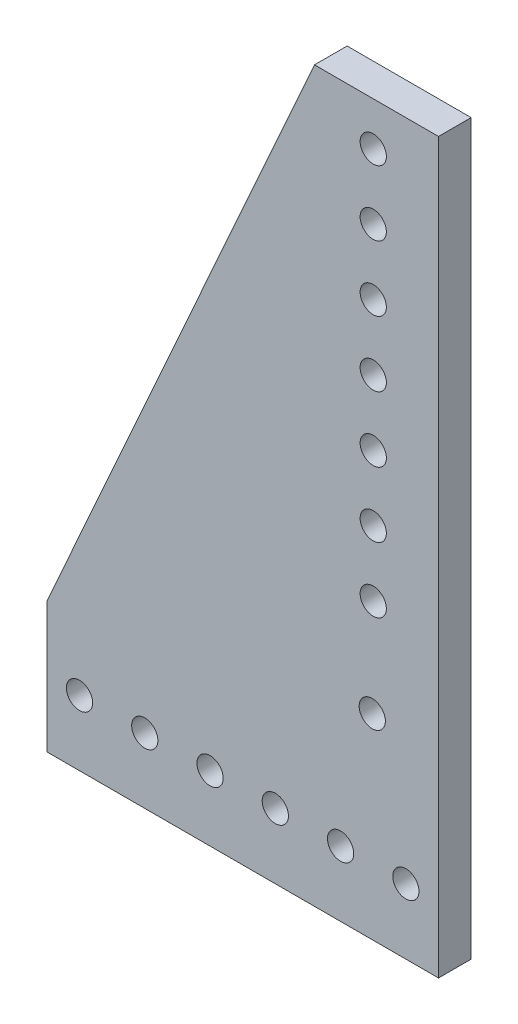
SolidWorks part; units mm, degrees
material "6061-T6 (SS)"
ref_plane "Front Plane" through (0, 0, 0) normal (0, 0, 1) x (1, 0, 0)
ref_plane "Top Plane" through (0, 0, 0) normal (0, 1, 0) x (1, 0, 0)
ref_plane "Right Plane" through (0, 0, 0) normal (1, 0, 0) x (0, 0, -1)
sketch "Sketch1" plane through (0, 0, 0) normal (0, 0, 1) x (1, 0, 0)
  line L1 (-128, 138.6667) -> (49.8, 138.6667)
  line L2 (-128, 138.6667) -> (-128, -115.3333)
  line L3 (-128, -115.3333) -> (49.8, -115.3333)
  line L4 (49.8, 138.6667) -> (49.8, -115.3333)
  dimension "D1" = 254
  dimension "D2" = 177.8
extrude "Boss-Extrude1" add sketch "Sketch1" along normal blind 6.35
sketch "Sketch2" plane through (0, 0, 6.35) normal (0, 0, 1) x (1, 0, 0)
  line L0 (-39.1, -115.3333) -> (-39.1, 138.6667) construction
  line L1 (-128, -115.3333) -> (49.8, -115.3333) construction
  line L2 (49.8, 138.6667) -> (-128, 138.6667) construction
  line L3 (-39.1, -108.9833) -> (-39.1, -96.2833) construction
  circle A0 centre (-39.1, -108.9833) radius 2.5527 construction
  circle A1 centre (-39.1, -96.2833) radius 2.5527 construction
  circle A2 centre (-39.1, -83.5833) radius 2.5527 construction
  circle A3 centre (-39.1, -70.8833) radius 2.5527 construction
  circle A4 centre (-39.1, -58.1833) radius 2.5527
  circle A5 centre (-39.1, -45.4833) radius 2.5527
  circle A6 centre (-39.1, -32.7833) radius 2.5527
  circle A7 centre (-39.1, -20.0833) radius 2.5527
  circle A8 centre (-39.1, -7.3833) radius 2.5527
  circle A9 centre (-39.1, 5.3167) radius 2.5527
  circle A10 centre (-39.1, 18.0167) radius 2.5527
  circle A11 centre (-39.1, 30.7167) radius 2.5527
  circle A12 centre (-39.2905, -77.2333) radius 2.5527
  dimension "D1" = 6.35
  dimension "D2" = 5.1054
  dimension "D5" = 5.1054
  dimension "D6" = 19.05
  dimension "D3" = 12.7
  dimension "D4" = 12
extrude "Cut-Extrude1" cut sketch "Sketch2" against normal through all
sketch "Sketch3" plane through (0, 0, 6.35) normal (0, 0, 1) x (1, 0, 0)
  line L0 (30.75, -102.6333) -> (-17.6342, -102.6333) construction
  line L1 (-128, -115.3333) -> (49.8, -115.3333) construction
  line L2 (49.8, -115.3333) -> (49.8, 138.6667) construction
  line L3 (30.75, -102.6333) -> (18.05, -102.6333) construction
  circle A0 centre (30.75, -102.6333) radius 2.5527
  circle A1 centre (18.05, -102.6333) radius 2.5527
  circle A2 centre (5.35, -102.6333) radius 2.5527
  circle A3 centre (-7.35, -102.6333) radius 2.5527
  circle A4 centre (-20.05, -102.6333) radius 2.5527
  circle A5 centre (-32.75, -102.6333) radius 2.5527
  circle A6 centre (-45.45, -102.6333) radius 2.5527
  circle A7 centre (-58.15, -102.6333) radius 2.5527
  circle A8 centre (-70.85, -102.6333) radius 2.5527
  circle A9 centre (-83.55, -102.6333) radius 2.5527
  circle A10 centre (-96.25, -102.6333) radius 2.5527
  circle A11 centre (-108.95, -102.6333) radius 2.5527
  dimension "D3" = 5.1054
  dimension "D1" = 12.7
  dimension "D2" = 19.05
  dimension "D4" = 12.7
extrude "Cut-Extrude2" cut sketch "Sketch3" against normal through all
sketch "Sketch4" plane through (0, 0, 6.35) normal (0, 0, 1) x (1, 0, 0)
  line L0 (-128, -115.3333) -> (-102.6, -115.3333)
  line L1 (-128, -115.3333) -> (49.8, -115.3333) construction
  line L2 (-102.6, -115.3333) -> (-102.6, -89.9333)
  line L3 (-102.6, -89.9333) -> (-50.53, 26.4641)
  line L4 (-50.53, 26.4641) -> (-26.4, 26.4641)
  line L5 (-26.4, 26.4641) -> (-26.4, -89.9333)
  line L6 (-26.4, -89.9333) -> (-26.4, -115.3333)
  line L7 (-26.4, -115.3333) -> (49.8, -115.3333)
  line L8 (49.8, -115.3333) -> (49.8, 138.6667)
  line L9 (49.8, 138.6667) -> (-128, 138.6667)
  line L10 (-128, 138.6667) -> (-128, -115.3333)
  dimension "D1" = 25.4
  dimension "D2" = 76.2
  dimension "D3" = 24.13
  dimension "D6" = 25.4
  dimension "D7" = 25.4
extrude "Cut-Extrude3" cut sketch "Sketch4" against normal through all
